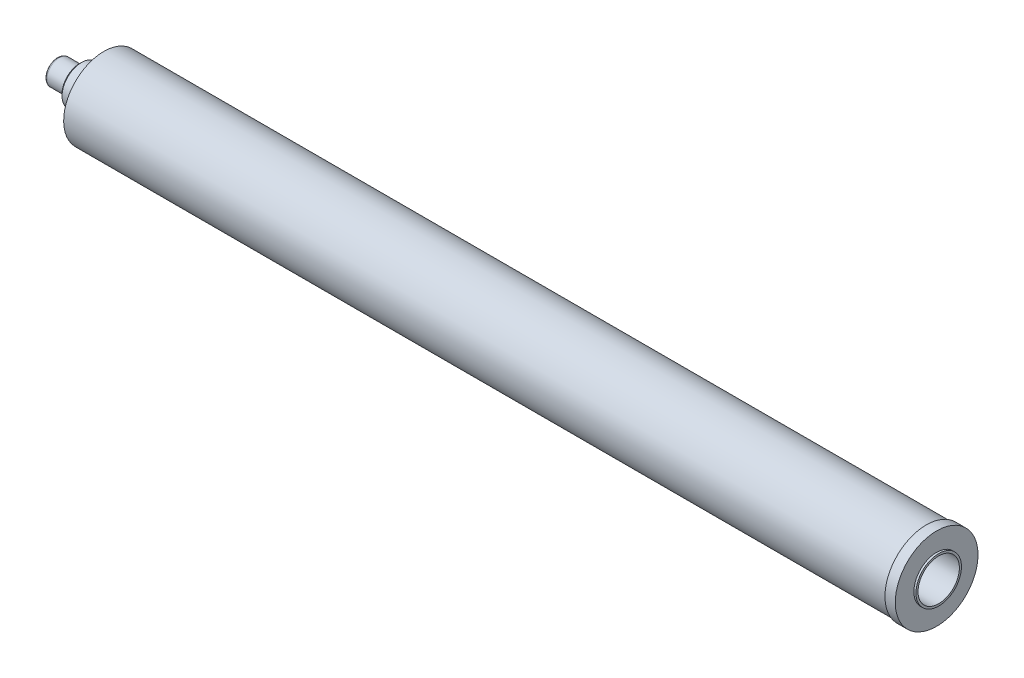
SolidWorks part; units mm, degrees
material "6061 Alloy"
ref_plane "Front Plane" through (0, 0, 0) normal (0, 0, 1) x (1, 0, 0)
ref_plane "Top Plane" through (0, 0, 0) normal (0, 1, 0) x (1, 0, 0)
ref_plane "Right Plane" through (0, 0, 0) normal (1, 0, 0) x (0, 0, -1)
sketch "Sketch1" plane through (0, 0, 0) normal (0, 0, 1) x (1, 0, 0)
  line L0 (0, 0) -> (0, 15.24)
  line L1 (0, 15.24) -> (27.305, 15.24)
  line L2 (27.305, 15.24) -> (27.305, 23.876)
  line L3 (27.305, 23.876) -> (57.15, 23.876)
  line L4 (57.15, 23.876) -> (57.15, 49.2125)
  line L5 (57.15, 49.2125) -> (1067.054, 49.2125)
  line L6 (1067.054, 49.2125) -> (1067.054, 50.8)
  line L7 (1067.054, 50.8) -> (1079.754, 50.8)
  line L8 (1079.754, 50.8) -> (1079.754, 0)
  line L9 (1079.754, 0) -> (0, 0)
  dimension "D1" = 12.7
  dimension "D2" = 50.8
  dimension "D3" = 49.2125
  dimension "D4" = 23.876
  dimension "D5" = 29.845
  dimension "D6" = 57.15
  dimension "D7" = 15.24
  dimension "D8" = 1009.904
revolve "Revolve1" add sketch "Sketch1" angle 360 about L9
hole_wizard "CSK for 3/8 Flat Head Machine Screw (100)1" positions "Sketch2" profile "Sketch3" countersink size "3/8" standard "ANSI Inch"
sketch "Sketch2" plane through (0, 0, 0) normal (-1, 0, 0) x (0, 0, 1)
  point P0 (0, 0)
sketch "Sketch3" plane through (0, 0, 0) normal (0, 1, 0) x (0, 0, 1)
  line L0 (0, 0) -> (0, 28.4295)
  line L1 (0, 28.4295) -> (5.0419, 25.4)
  line L2 (5.0419, 25.4) -> (5.0419, 3.8896)
  line L3 (5.0419, 3.8896) -> (9.6774, 0)
  line L5 (9.6774, 0) -> (0, 0)
  line L6 (-5.0419, 3.8896) -> (-9.6774, 0) construction
  line L10 (0, 28.4295) -> (-5.0419, 25.4) construction
  line L11 (0, -6.35) -> (0, 107.95) construction
  dimension "Hole Dia." = 10.0838
  dimension "Hole Depth" = 25.4
  dimension "Near C'Sink Dia." = 19.3548
  dimension "Near C'Sink Angle" = 100
  dimension "Drill Angle" = 118
fillet "Fillet1" radius 2.54 1 edges at (0, 15.24, 0)
chamfer "Chamfer1" distance 2.54 angle 45 1 edges at (27.305, 23.876, 0)
sketch "Sketch4" plane through (1079.754, 0, 0) normal (1, 0, 0) x (0, 0, -1)
  circle A0 centre (0, 0) radius 25.4
  circle A1 centre (0, 0) radius 27.94
  dimension "D1" = 50.8
  dimension "D2" = 55.88
extrude "Boss-Extrude1" add sketch "Sketch4" along normal blind 2.54
sketch "Sketch5" plane through (1082.294, 0, 0) normal (1, 0, 0) x (0, 0, -1)
  circle A0 centre (0, 0) radius 25.4 construction
  circle A1 centre (0, 0) radius 25.4
extrude "Cut-Extrude1" cut sketch "Sketch5" against normal blind 508
